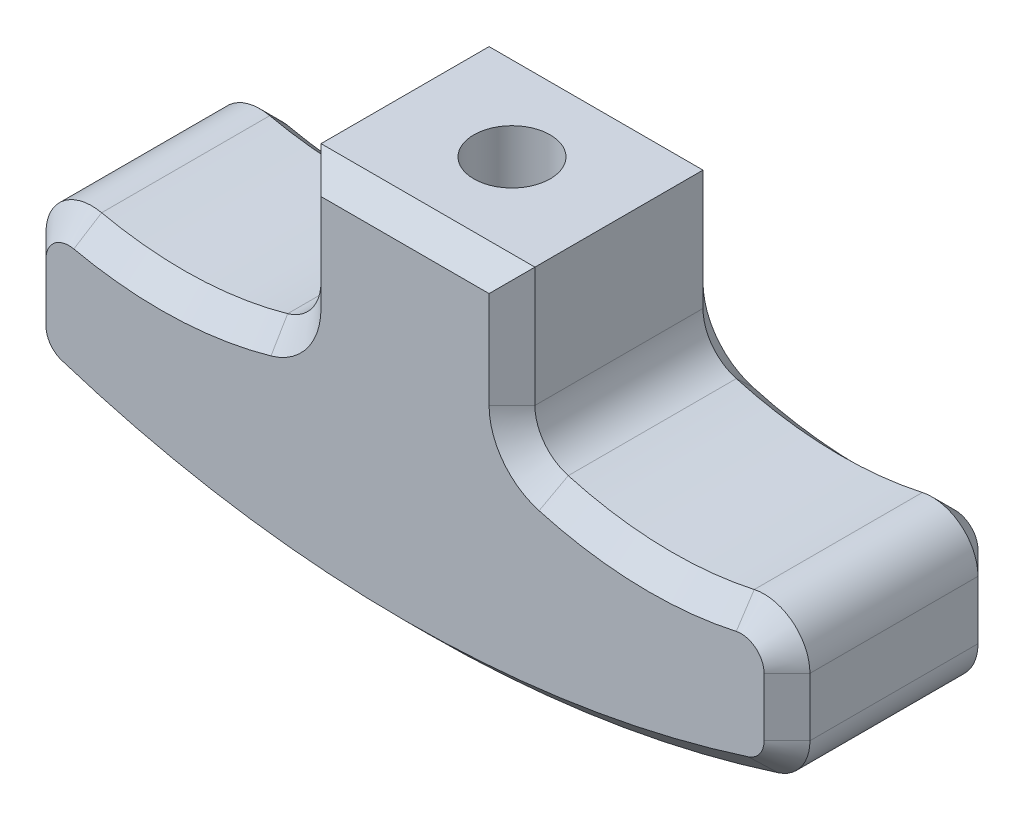
SolidWorks part; units mm, degrees
material "3D printed plastic"
ref_plane "Front Plane" through (0, 0, 0) normal (0, 0, 1) x (1, 0, 0)
ref_plane "Top Plane" through (0, 0, 0) normal (0, 1, 0) x (1, 0, 0)
ref_plane "Right Plane" through (0, 0, 0) normal (1, 0, 0) x (0, 0, -1)
sketch "Sketch1" plane through (0, 0, 0) normal (0, 0, 1) x (1, 0, 0)
  line L0 (-7, -10) -> (-25, -10) construction
  line L1 (-7, 0) -> (7, 0)
  line L2 (-7, 0) -> (-7, -10)
  line L4 (7, 0) -> (7, -10)
  line L5 (25, -10) -> (7, -10) construction
  line L6 (25, -10) -> (25, -20)
  line L7 (25, -20) -> (-25, -20) construction
  line L8 (-25, -10) -> (-25, -20)
  arc A0 (-25, -20) -> (25, -20) centre (0, 50.7107) ccw
  arc A1 (-25, -10) -> (-7, -10) centre (-16, 13.3238) ccw
  arc A2 (7, -10) -> (25, -10) centre (16, 13.3238) ccw
  dimension "D1" = 14
  dimension "D5" = 25
  dimension "D6" = 75
  dimension "D2" = 50
  dimension "D3" = 10
  dimension "D4" = 10
extrude "Boss-Extrude1" add sketch "Sketch1" along normal mid plane 14
fillet "Fillet1" radius 3 6 edges at (-25, -20, 0) (25, -20, 0) (25, -10, 0) (7, -10, 0) (-7, -10, 0) (-25, -10, 0)
chamfer "Chamfer1" distance 1.5 angle 45 28 edges at (24.4238, -19.6136, -7) (25, -15.9358, -7) (23.8803, -11.6882, -7) (15.2468, -11.6648, -7) (7.6068, -9.6513, -7) (7, -3.9211, -7) (0, 0, -7) (-7, -3.9211, -7) (-7.6068, -9.6513, -7) (-15.2468, -11.6648, -7) (-23.8803, -11.6882, -7) (-25, -15.9358, -7) (-24.4238, -19.6136, -7) (0, -24.2893, -7) (-23.8803, -11.6882, 7) (-15.2468, -11.6648, 7) (-7.6068, -9.6513, 7) (-7, -3.9211, 7) (0, 0, 7) (7, -3.9211, 7) (7.6068, -9.6513, 7) (15.2468, -11.6648, 7) (23.8803, -11.6882, 7) (25, -15.9358, 7) (24.4238, -19.6136, 7) (0, -24.2893, 7) (-24.4238, -19.6136, 7) (-25, -15.9358, 7)
sketch "Sketch2" plane through (0, 0, 0) normal (0, 1, 0) x (1, 0, 0)
  circle A0 centre (0, 0) radius 2.5
  dimension "D1" = 5
extrude "Cut-Extrude1" cut sketch "Sketch2" against normal through all
sketch "Sketch3" plane through (0, 0, 0) normal (0, 1, 0) x (1, 0, 0)
  circle A0 centre (0, 0) radius 5
  dimension "D1" = 10
extrude "Cut-Extrude2" cut sketch "Sketch3" against normal through all from offset 17 offset against normal yes
